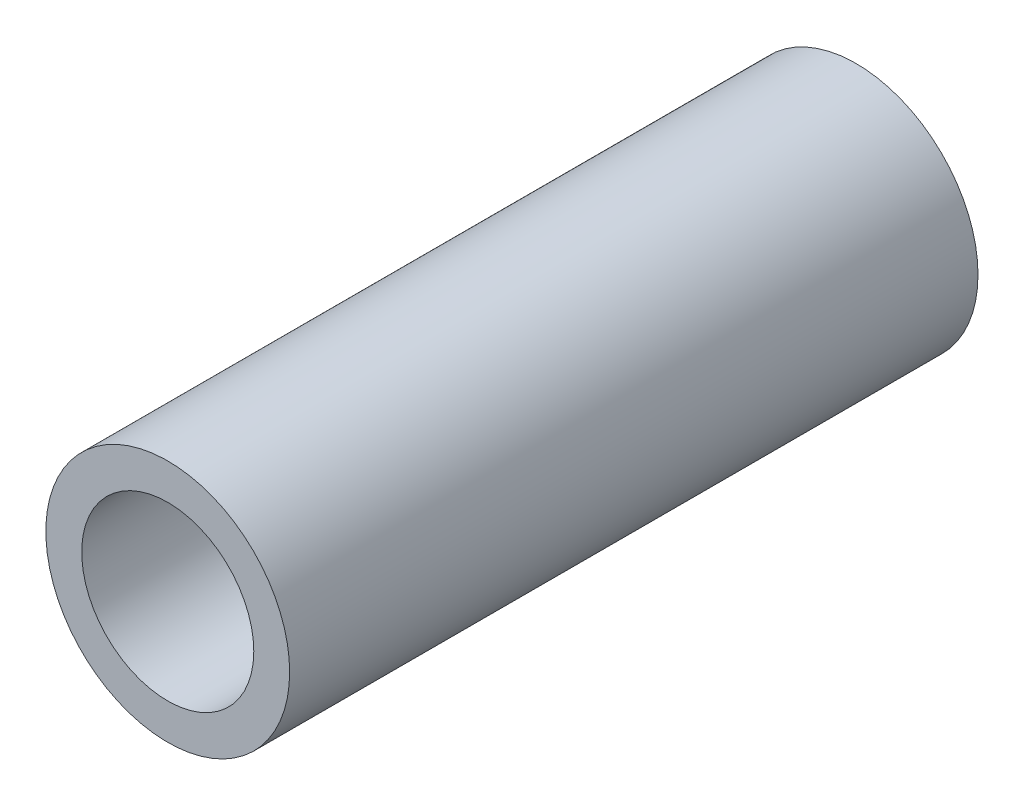
SolidWorks part; units mm, degrees
material "Silicon Rubber"
ref_plane "X-Y Datum" through (0, 0, 0) normal (0, 0, 1) x (1, 0, 0)
ref_plane "X-Z Datum" through (0, 0, 0) normal (0, 1, 0) x (1, 0, 0)
ref_plane "Y-Z Datum" through (0, 0, 0) normal (1, 0, 0) x (0, 0, -1)
sketch3d "3DSketch1"
  line L0 (0, 0, 0) -> (0, 0, 76.2)
  dimension "D1" = 76.2
sweep "Sweep1" add path "3DSketch1" circular profile diameter 26.9875 parameters "D3"=26.9875
sweep "Cut-Sweep1" cut path "3DSketch1<2>" circular profile diameter 19.05 parameters "D3"=19.05
sketch3d "3DSketch1<2>" same geometry as "3DSketch1"
